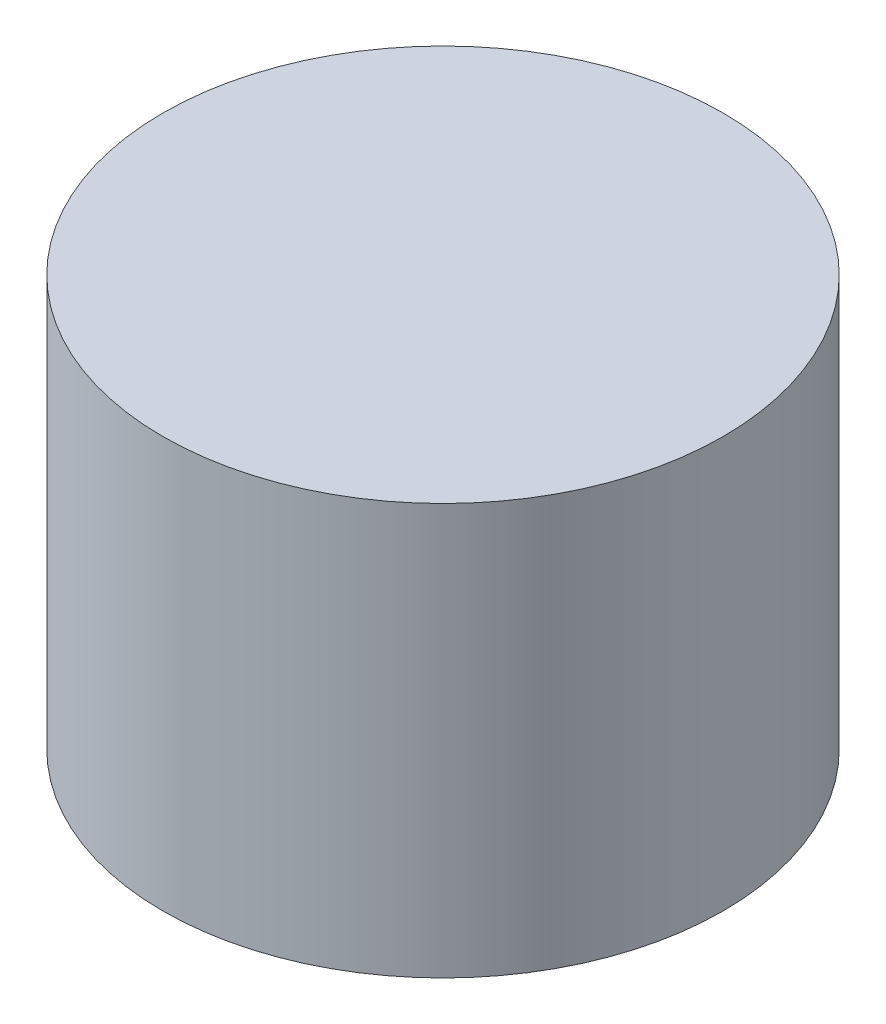
SolidWorks part; units mm, degrees
material "201.0-T7 Insulated Mold Casting (SS)"
ref_plane "Front" through (0, 0, 0) normal (0, 0, 1) x (1, 0, 0)
ref_plane "Top" through (0, 0, 0) normal (0, 1, 0) x (1, 0, 0)
ref_plane "Right" through (0, 0, 0) normal (1, 0, 0) x (0, 0, -1)
sketch "Sketch1" plane through (0, 0, 0) normal (0, 1, 0) x (1, 0, 0)
  circle A0 centre (0, 0) radius 7.5
extrude "Boss-Extrude1" add sketch "Sketch1" along normal blind 13
sketch "Sketch2" plane through (0, 0, 0) normal (0, -1, 0) x (1, 0, 0)
  circle A0 centre (0, 0) radius 6.5
extrude "Cut-Extrude1" cut sketch "Sketch2" against normal blind 7
sketch "Sketch3" plane through (0, 7, 0) normal (0, -1, 0) x (1, 0, 0)
  line L1 (-4, 2.5) -> (4, 2.5)
  line L2 (-4, 2.5) -> (-4, -2.5)
  line L3 (-4, -2.5) -> (4, -2.5)
  line L4 (4, 2.5) -> (4, -2.5)
  line L5 (-4, 2.5) -> (4, -2.5) construction
  line L6 (-4, -2.5) -> (4, 2.5) construction
  point P0 (0, 0)
  dimension "D1" = 5
  dimension "D2" = 8
extrude "Cut-Extrude2" cut sketch "Sketch3" against normal blind 5
sketch "Sketch5" plane through (0, 7, 0) normal (0, -1, 0) x (1, 0, 0)
  circle A0 centre (0, 0) radius 5
extrude "Cut-Extrude5" cut sketch "Sketch5" against normal blind 5
ref_plane "Plane2" through (0, 0, 7) normal (0, 0, 1) x (1, 0, 0)
sketch "Sketch7" plane through (0, 0, 7) normal (0, 0, 1) x (1, 0, 0)
  line L0 (11.0397, 8) -> (-15.0427, 8) construction
  line L1 (-7.5, 0) -> (7.5, 0) construction
  circle A1 centre (0, 8) radius 0.9
  dimension "D1" = 8
extrude "Boss-Extrude4" add sketch "Sketch7" against normal blind 14
ref_plane "Plane4" through (0, 0, 2) normal (0, 0, 1) x (1, 0, 0)
sketch "Sketch10" plane through (0, 0, 2) normal (0, 0, 1) x (1, 0, 0)
  line L0 (11.9143, 8) -> (-12.7116, 8) construction
  line L1 (-7.5, 0) -> (7.5, 0) construction
  circle A0 centre (0, 8) radius 2
  dimension "D1" = 8
extrude "Boss-Extrude5" add sketch "Sketch10" along normal blind 5
ref_plane "Plane5" through (0, 0, -2) normal (0, 0, 1) x (1, 0, 0)
sketch "Sketch11" plane through (0, 0, -2) normal (0, 0, 1) x (1, 0, 0)
  line L0 (11.4572, 8) -> (-12.5781, 8) construction
  line L1 (-7.5, 0) -> (7.5, 0) construction
  circle A0 centre (0, 8) radius 2
  dimension "D1" = 8
extrude "Boss-Extrude6" add sketch "Sketch11" against normal blind 5
sketch "Sketch13" plane through (0, 0, 0) normal (0, -1, 0) x (1, 0, 0)
  circle A0 centre (0, 0) radius 7.5
extrude "Cut-Extrude6" cut sketch "Sketch13" against normal blind 2
chamfer "Chamfer1" distance 1 angle 45 1 edges at (0, 2, -6.5)
